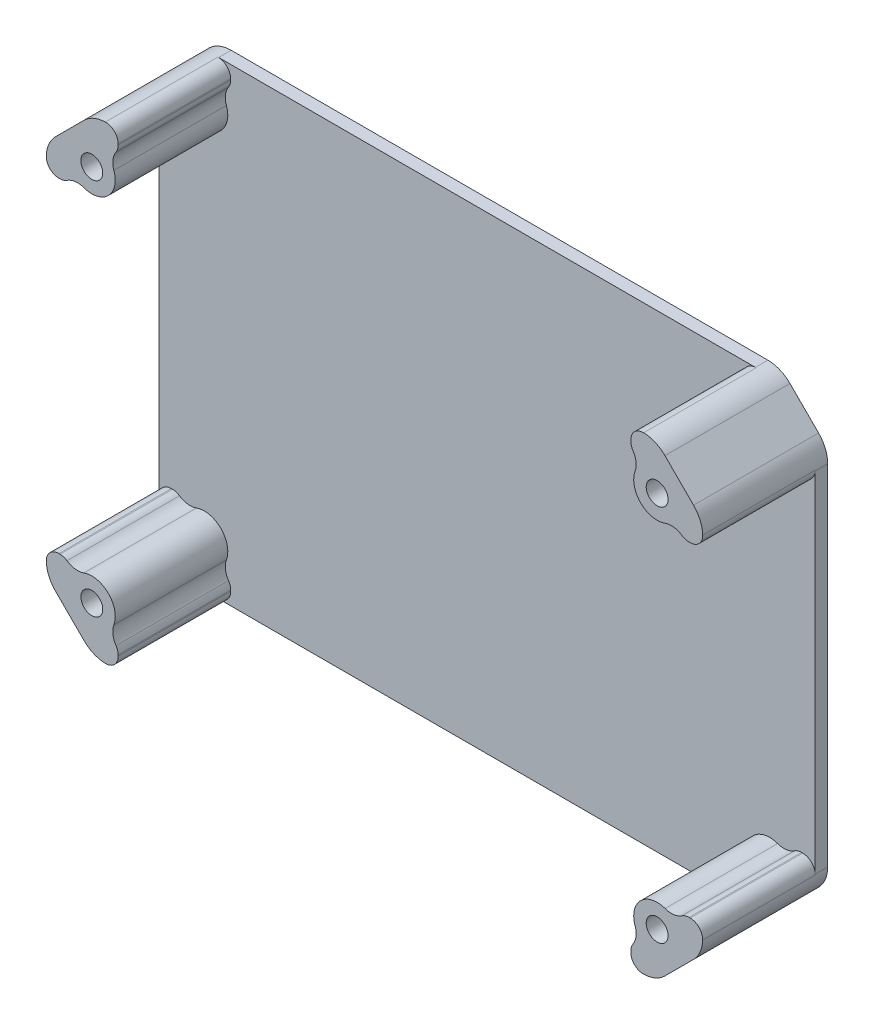
SolidWorks part; units mm, degrees
material "ABS"
ref_plane "Спереди" through (0, 0, 0) normal (0, 0, 1) x (1, 0, 0)
ref_plane "Сверху" through (0, 0, 0) normal (0, 1, 0) x (1, 0, 0)
ref_plane "Справа" through (0, 0, 0) normal (1, 0, 0) x (0, 0, -1)
sketch "Эскиз1" plane through (0, 0, 0) normal (0, 0, 1) x (1, 0, 0)
  line L0 (-52.5, 30) -> (-45, 37.5)
  line L1 (-45, 37.5) -> (45, 37.5)
  line L2 (-52.5, 30) -> (-52.5, -30)
  line L3 (-45, -37.5) -> (45, -37.5)
  line L4 (52.5, 30) -> (52.5, -30)
  line L5 (-52.5, 37.5) -> (52.5, -37.5) construction
  line L6 (-52.5, -37.5) -> (52.5, 37.5) construction
  line L7 (45, 37.5) -> (52.5, 30)
  line L8 (45, -37.5) -> (52.5, -30)
  line L9 (-52.5, -30) -> (-45, -37.5)
  point P0 (0, 0)
  dimension "D1" = 75
  dimension "D2" = 105
extrude "Бобышка-Вытянуть1" add sketch "Эскиз1" along normal blind 20
sketch "Эскиз2" plane through (0, 0, 20) normal (0, 0, 1) x (1, 0, 0)
  line L0 (-48.75, 33.75) -> (-38.4079, 23.4079) construction
  line L1 (-45, 37.5) -> (-52.5, 30) construction
  line L2 (-52.5, 0) -> (52.5, 0) construction
  line L3 (-52.5, 30) -> (-52.5, -30) construction
  line L4 (52.5, -30) -> (52.5, 30) construction
  line L5 (0, 37.5) -> (0, -37.5) construction
  line L6 (45, 37.5) -> (-45, 37.5) construction
  line L7 (-45, -37.5) -> (45, -37.5) construction
  line L8 (48.75, 33.75) -> (38.4079, 23.4079) construction
  line L9 (48.75, -33.75) -> (38.4079, -23.4079) construction
  line L10 (-48.75, -33.75) -> (-38.4079, -23.4079) construction
  circle A0 centre (-45.2145, 30.2145) radius 1.75
  circle A1 centre (45.2145, 30.2145) radius 1.75
  circle A2 centre (45.2145, -30.2145) radius 1.75
  circle A3 centre (-45.2145, -30.2145) radius 1.75
  dimension "D1" = 3.5
  dimension "D2" = 5
extrude "Вырез-Вытянуть1" cut sketch "Эскиз2" against normal blind 34
shell "Оболочка1" thickness 2 removed face at (-46.9645, -30.2145, 20)
fillet "Скругление1" radius 10 8 edges at (-45.7448, -33.9268, 11) (-48.9268, -30.7448, 11) (48.9268, -30.7448, 11) (45.7448, -33.9268, 11) (45.7448, 33.9268, 11) (48.9268, 30.7448, 11) (-45.7448, 33.9268, 11) (-48.9268, 30.7448, 11)
fillet "Скругление2" radius 3 8 edges at (-50.5, 29.1716, 11) (-44.1716, 35.5, 11) (-44.1716, -35.5, 11) (-50.5, -29.1716, 11) (44.1716, -35.5, 11) (50.5, -29.1716, 11) (50.5, 29.1716, 11) (44.1716, 35.5, 11)
fillet "Скругление3" radius 5 8 edges at (-52.5, 30, 10) (-45, 37.5, 10) (45, 37.5, 10) (52.5, 30, 10) (52.5, -30, 10) (45, -37.5, 10) (-52.5, -30, 10) (-45, -37.5, 10)
ref_plane "Плоскость1" through (42.9289, -37.5, 20) normal (1, 0, 0) x (0, 0, -1)
sketch "Эскиз4" plane through (0, 0, 20) normal (0, 0, 1) x (1, 0, 0)
  line L1 (-41, 63.3728) -> (41, 63.3728)
  line L2 (-41, 63.3728) -> (-41, -63.3728)
  line L3 (-41, -63.3728) -> (41, -63.3728)
  line L4 (41, 63.3728) -> (41, -63.3728)
  line L5 (-41, 63.3728) -> (41, -63.3728) construction
  line L6 (-41, -63.3728) -> (41, 63.3728) construction
  point P0 (0, 0)
  dimension "D1" = 82
extrude "Вырез-Вытянуть2" cut sketch "Эскиз4" against normal up to surface (18 mm away) up to face at (0, 0, 2)
fillet "Скругление4" radius 2 8 edges at (41, -34.6057, 11) (41, -37.5, 11) (-41, -34.6057, 11) (-41, -37.5, 11) (-41, 34.6057, 11) (-41, 37.5, 11) (41, 34.6057, 11) (41, 37.5, 11)
sketch "Эскиз5" plane through (0, 0, 20) normal (0, 0, 1) x (1, 0, 0)
  line L1 (-86.9479, 26) -> (86.9479, 26)
  line L2 (-86.9479, 26) -> (-86.9479, -26)
  line L3 (-86.9479, -26) -> (86.9479, -26)
  line L4 (86.9479, 26) -> (86.9479, -26)
  line L5 (-86.9479, 26) -> (86.9479, -26) construction
  line L6 (-86.9479, -26) -> (86.9479, 26) construction
  point P0 (0, 0)
  dimension "D1" = 52
extrude "Вырез-Вытянуть3" cut sketch "Эскиз5" against normal up to surface (18 mm away)
fillet "Скругление5" radius 2 8 edges at (49.6057, -26, 11) (52.5, -26, 11) (49.6057, 26, 11) (52.5, 26, 11) (-49.6057, -26, 11) (-52.5, -26, 11) (-49.6057, 26, 11) (-52.5, 26, 11)
